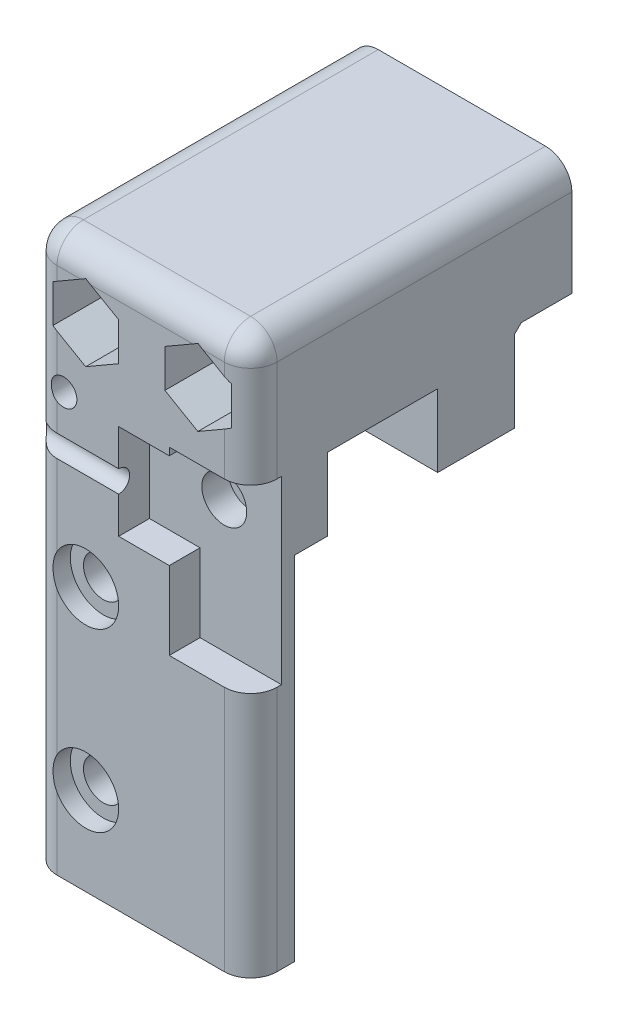
SolidWorks part; units mm, degrees
ref_plane "Front Plane" through (0, 0, 0) normal (0, 0, 1) x (1, 0, 0)
ref_plane "Top Plane" through (0, 0, 0) normal (0, 1, 0) x (1, 0, 0)
ref_plane "Right Plane" through (0, 0, 0) normal (1, 0, 0) x (0, 0, -1)
sketch "Sketch1" plane through (0, 0, 0) normal (1, 0, 0) x (0, 0, -1)
  line L1 (8.75, 0) -> (8.75, 9.25)
  line L2 (8.75, 9.25) -> (9.5, 10)
  line L3 (9.5, 10) -> (15.25, 10)
  line L4 (15.25, 10) -> (15.25, 23)
  line L5 (15.25, 23) -> (-19.25, 23)
  line L6 (-19.25, 23) -> (-19.25, -40)
  line L7 (-19.25, -40) -> (-16.25, -40)
  line L8 (-16.25, -40) -> (-16.25, 0)
  line L9 (-16.25, 0) -> (-12.5, 0)
  line L13 (0, 0) -> (3.75, 0)
  line L15 (-12.5, 0) -> (-12.25, 0) construction
  line L16 (-12.25, 0) -> (-12.25, 8) construction
  line L17 (-12.25, 8) -> (-0.25, 8) construction
  line L18 (-0.25, 8) -> (-0.25, 0) construction
  line L19 (-0.25, 0) -> (0, 0) construction
  line L20 (-12.5, 0) -> (-12.5, 8.25)
  line L21 (-12.5, 8.25) -> (0, 8.25)
  line L22 (0, 8.25) -> (0, 0)
  line L23 (8.75, 8) -> (8.75, -22) construction
  line L24 (3.75, 0) -> (8.75, 0)
  line L25 (15.25, 23) -> (15.25, 10) construction
  line L26 (15.25, 10) -> (10.75, 10) construction
  line L27 (47.75, 23) -> (15.25, 23) construction
  point P0 (0, 0)
  dimension "D3" = 12
  dimension "D4" = 8
  dimension "D1" = 20
  dimension "D5" = 225
  dimension "D6" = 0.75
  dimension "D7" = 40
  dimension "D8" = 3
extrude "Boss-Extrude1" add sketch "Sketch1" along normal blind 25
sketch "Sketch2" plane through (0, 0, 19.25) normal (0, 0, 1) x (1, 0, 0)
  line L0 (6.25, -40) -> (6.25, -30) construction
  line L2 (6.25, -30) -> (6.25, -20) construction
  line L3 (6.25, -20) -> (6.25, -10) construction
  line L4 (25, -40) -> (0, -40) construction
  line L5 (6.25, 23) -> (6.25, 16) construction
  line L6 (25, 23) -> (0, 23) construction
  line L7 (6.25, 16) -> (6.25, -10) construction
  line L8 (6.25, 16) -> (19, 16) construction
  line L9 (19, 16) -> (25, 16) construction
  line L10 (25, 23) -> (25, -40) construction
  circle A0 centre (6.25, -30) radius 2.25
  circle A1 centre (6.25, -10) radius 2 construction
  circle A2 centre (6.25, -10) radius 2.25
  circle A3 centre (6.25, 16) radius 2.25
  circle A5 centre (19, 16) radius 2.25
  dimension "D2" = 4
  dimension "D1" = 10
  dimension "D4" = 7
  dimension "D5" = 6
  dimension "D6" = 12.75
  dimension "D3" = 0.25
extrude "Cut-Extrude1" cut sketch "Sketch2" against normal up to next
sketch "Sketch3" plane through (0, 0, 19.25) normal (0, 0, 1) x (1, 0, 0)
  line L0 (10, 18.1651) -> (6.25, 20.3301)
  line L1 (9.75, 18.0207) -> (6.25, 20.0415) construction
  line L2 (6.25, 20.0415) -> (2.75, 18.0207) construction
  line L3 (2.75, 18.0207) -> (2.75, 13.9793) construction
  line L4 (0, 23) -> (0, -40)
  line L5 (0, -40) -> (25, -40)
  line L6 (25, -40) -> (25, 23)
  line L7 (25, 23) -> (0, 23)
  line L8 (0, 23) -> (0, -40)
  line L9 (0, -40) -> (25, -40)
  line L10 (25, -40) -> (25, 23)
  line L11 (25, 23) -> (0, 23)
  line L12 (2.75, 13.9793) -> (6.25, 11.9585) construction
  line L13 (6.25, 11.9585) -> (9.75, 13.9793) construction
  line L14 (9.75, 13.9793) -> (9.75, 18.0207) construction
  line L15 (6.25, 20.3301) -> (2.5, 18.1651)
  line L16 (2.5, 18.1651) -> (2.5, 13.8349)
  line L17 (2.5, 13.8349) -> (6.25, 11.6699)
  line L18 (6.25, 11.6699) -> (10, 13.8349)
  line L19 (10, 13.8349) -> (10, 18.1651)
  line L21 (19, 20.3301) -> (15.25, 18.1651)
  line L22 (15.25, 18.1651) -> (15.25, 13.8349)
  line L23 (15.25, 13.8349) -> (19, 11.6699)
  line L24 (19, 11.6699) -> (22.75, 13.8349)
  line L25 (22.75, 13.8349) -> (22.75, 18.1651)
  line L26 (22.75, 18.1651) -> (19, 20.3301)
  circle A0 centre (6.25, -10) radius 3.5 construction
  circle A1 centre (6.25, -30) radius 3.75
  circle A2 centre (6.25, -10) radius 2.25 construction
  circle A3 centre (6.25, -30) radius 2.25 construction
  circle A4 centre (6.25, -10) radius 3.75
  circle A6 centre (19, 16) radius 3.75 construction
  circle A7 centre (6.25, 16) radius 3.5 construction
  circle A8 centre (6.25, 16) radius 2.25 construction
  circle A9 centre (19, 16) radius 2.25 construction
  dimension "D3" = 7
  dimension "D4" = 7
extrude "Boss-Extrude2" add sketch "Sketch3" along normal blind 2
fillet "Fillet1" radius 3 5 edges at (0, 23, 3) (25, 23, 3) (12.5, 23, 21.25) (25, -8.5, 21.25) (0, -8.5, 21.25)
sketch "Sketch4" plane through (0, 0, 21.25) normal (0, 0, 1) x (1, 0, 0)
  line L0 (25, 8.25) -> (25, 16) construction
  line L1 (16, -11.75) -> (25, -11.75) construction
  line L2 (16, -11.75) -> (16, 8.25) construction
  line L3 (16, 8.25) -> (25, 8.25) construction
  line L5 (16, -11.75) -> (25, 8.25) construction
  line L6 (16, 8.25) -> (25, -11.75) construction
  line L7 (15.75, -12) -> (25, -12)
  line L8 (15.75, -12) -> (15.75, -3.15)
  line L9 (15.75, 8.5) -> (25, 8.5)
  line L10 (25, 8.5) -> (25, -12)
  line L11 (18.5, 8.25) -> (18.5, 3) construction
  line L12 (18.5, 3) -> (18.5, -6.5) construction
  line L13 (18.5, -6.5) -> (18.5, -11.75) construction
  line L14 (15.75, 7.65) -> (10, 7.65)
  line L15 (10, 7.65) -> (10, -3.15)
  line L16 (10, -3.15) -> (15.75, -3.15)
  line L17 (15.75, 7.65) -> (15.75, 8.5)
  line L18 (15.75, -12) -> (15.75, 8.5) construction
  line L19 (15.75, -3.15) -> (15.75, 7.65) construction
  line L20 (16, 6.65) -> (11.5, 6.65) construction
  line L21 (16, -2.15) -> (11.5, -2.15) construction
  line L22 (11.5, 6.65) -> (11.5, 7.65) construction
  line L23 (11.5, -2.15) -> (11.5, -3.15) construction
  circle A0 centre (18.5, 3) radius 2.3 construction
  circle A2 centre (18.5, 3) radius 2.55
  point P0 (20.5, -1.75)
  dimension "D3" = 0.25
  dimension "D7" = 4.6
  dimension "D1" = 9
  dimension "D2" = 20
  dimension "D4" = 9.5
  dimension "D5" = 2.5
  dimension "D8" = 1.6
  dimension "D9" = 1
  dimension "D10" = 4.5
  dimension "D11" = 8.8
  dimension "D12" = 1.5
  dimension "D6" = 0.25
extrude "Cut-Extrude2" cut sketch "Sketch4" against normal offset from surface (3.5 mm away) 1.5 up to face at (8.5, -30, 16.25)
extrude "Cut-Extrude5" cut sketch "Sketch4<3>" against normal offset from surface (6.5 mm away) 3 contours A2 region at (18.5, 3, 21.25) up to face at (16.625, 0.25, 17.75) offset beyond the face yes
sketch "Sketch4<3>" plane through (0, 0, 21.25) normal (0, 0, 1) x (1, 0, 0) same geometry as "Sketch4"
sketch "Sketch6" plane through (0, 0, 21.25) normal (0, 0, 1) x (1, 0, 0)
  line L0 (10, 2.25) -> (0, 2.25) construction
  line L1 (10, 7.65) -> (10, -3.15) construction
  line L2 (0, 0) -> (0, 8.25) construction
  line L3 (0, 2.25) -> (0, 3.5)
  line L4 (0, 3.5) -> (10, 3.5)
  line L5 (10, 3.5) -> (10, 2.25)
  line L6 (10, 2.25) -> (0, 2.25)
  dimension "D1" = 2.5
revolve "Cut-Revolve1" cut sketch "Sketch6" angle 360 about L0
sketch "Sketch5" plane through (0, 0, 17.75) normal (0, 0, 1) x (1, 0, 0)
  line L0 (6.25, 10.6699) -> (6.25, 11.6699) construction
  line L1 (1, 5.1699) -> (6.5, 5.1699)
  line L2 (1, 5.1699) -> (1, 10.6699) construction
  line L3 (1, 10.6699) -> (6.5, 10.6699)
  line L4 (6.5, 5.1699) -> (6.5, 10.6699)
  line L5 (1, 5.1699) -> (6.5, 10.6699) construction
  line L6 (1, 10.6699) -> (6.5, 5.1699) construction
  line L7 (1, 5.1699) -> (0, 5.1699)
  line L8 (0, 0) -> (0, 8) construction
  line L9 (0, 5.1699) -> (0, 10.6699)
  line L10 (0, 10.6699) -> (1, 10.6699)
  circle A0 centre (3.75, 7.9199) radius 1.25 construction
  circle A1 centre (3.75, 7.9199) radius 1.5
  point P0 (3.75, 7.9199)
  dimension "D2" = 2.5
  dimension "D3" = 1
  dimension "D4" = 5.5
  dimension "D1" = 0.25
extrude "Cut-Extrude3" cut sketch "Sketch5" against normal mid plane 2
extrude "Cut-Extrude4" cut sketch "Sketch5<2>" against normal offset from surface 1.5 and the other way up to next contours A1 up to face at (12.5, 4.125, 12.5)
sketch "Sketch5<2>" plane through (0, 0, 17.75) normal (0, 0, 1) x (1, 0, 0) same geometry as "Sketch5"
sketch "Sketch7" plane through (0, 0, 19.25) normal (0, 0, 1) x (1, 0, 0)
  line L0 (22.75, 13.8349) -> (22.75, 18.1651) construction
  line L1 (22.75, 18.1651) -> (19, 20.3301) construction
  line L2 (19, 20.3301) -> (15.25, 18.1651) construction
  line L3 (15.25, 18.1651) -> (15.25, 13.8349) construction
  line L4 (15.25, 13.8349) -> (19, 11.6699) construction
  line L5 (19, 11.6699) -> (22.75, 13.8349) construction
  line L6 (6.25, 11.6699) -> (10, 13.8349) construction
  line L7 (10, 13.8349) -> (10, 18.1651) construction
  line L8 (10, 18.1651) -> (6.25, 20.3301) construction
  line L9 (6.25, 20.3301) -> (2.5, 18.1651) construction
  line L10 (2.5, 18.1651) -> (2.5, 13.8349) construction
  line L11 (2.5, 13.8349) -> (6.25, 11.6699) construction
  line L12 (22.75, 13.8349) -> (22.75, 18.1651)
  line L13 (22.75, 18.1651) -> (19, 20.3301)
  line L14 (19, 20.3301) -> (15.25, 18.1651)
  line L15 (15.25, 18.1651) -> (15.25, 13.8349)
  line L16 (15.25, 13.8349) -> (19, 11.6699)
  line L17 (19, 11.6699) -> (22.75, 13.8349)
  line L18 (6.25, 11.6699) -> (10, 13.8349)
  line L19 (10, 13.8349) -> (10, 18.1651)
  line L20 (10, 18.1651) -> (6.25, 20.3301)
  line L21 (6.25, 20.3301) -> (2.5, 18.1651)
  line L22 (2.5, 18.1651) -> (2.5, 13.8349)
  line L23 (2.5, 13.8349) -> (6.25, 11.6699)
extrude "Cut-Extrude6" cut sketch "Sketch7" against normal blind 10
equation "\"Tolerance\" = 0.25mm"
equation "\"Pocket_Head_M5\"= 8mm"
equation "\"Pocket_Head_M4\" = 7mm"
equation "\"Pocket_Nut_M4\" = 7mm"
equation "\"Pocket_Nut_M5\"= 8mm"
equation "\"Pocket_Nut_M3\"= 5.5mm"
equation "\"Pocket_Head_M3\"= 5.5mm"
equation "\"D2@Sketch1\"=\"Tolerance\""
equation "\"D3@Sketch2\"=\"Tolerance\""
equation "\"D3@Sketch3\"=\"Pocket_Head_M4\""
equation "\"D2@Sketch3\"=\"Tolerance\""
equation "\"D4@Sketch3\"=\"Pocket_Nut_M4\""
equation "\"D5@Sketch3\"=\"Tolerance\""
equation "\"D3@Sketch4\"=\"Tolerance\""
equation "\"D1@Sketch5\"=\"Tolerance\""
equation "\"D4@Sketch5\"=\"Pocket_Nut_M3\""
equation "\"D1@Cut-Extrude3\"=( 1.5 + ( \"Tolerance\" * 2 ) )"
equation "\"D6@Sketch4\"=\"Tolerance\""
